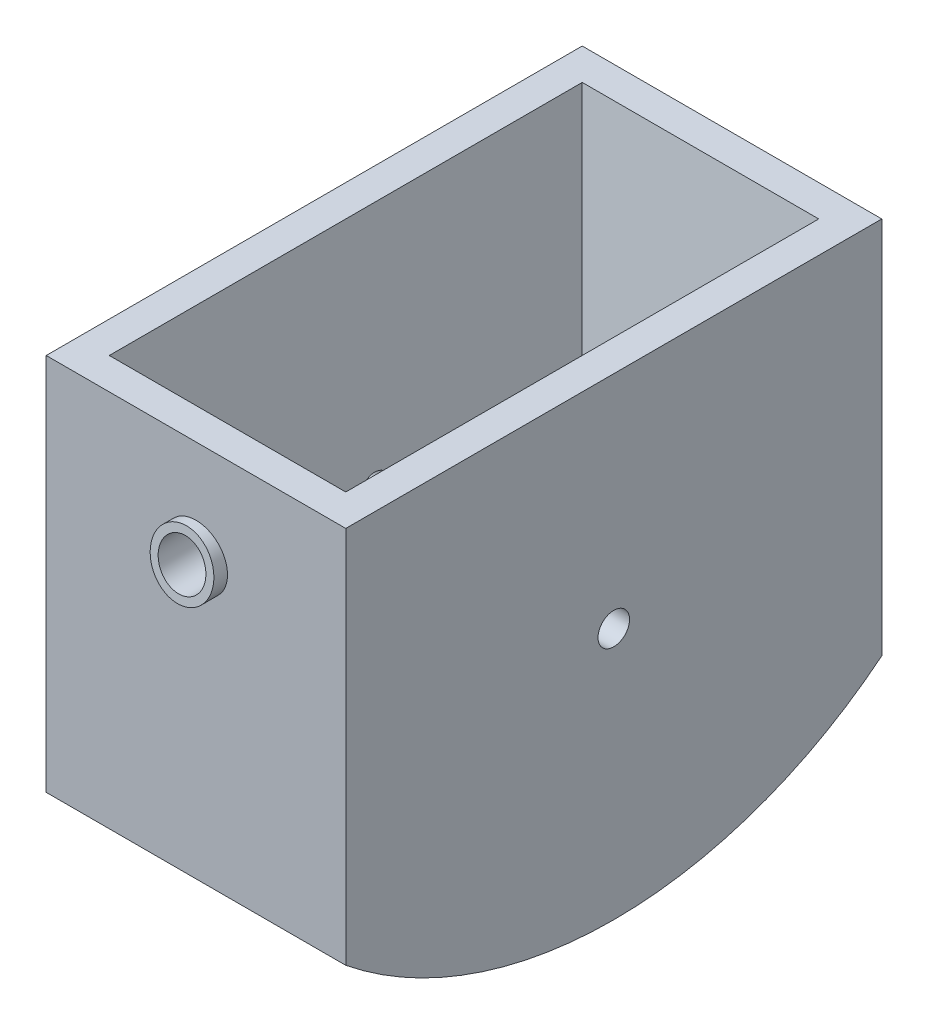
SolidWorks part; units mm, degrees
note: The reader was unsure of these and kept them because the rebuilt part matched: shared geometry of "Sketch2<3>".
ref_plane "Front Plane" through (0, 0, 0) normal (0, 0, 1) x (1, 0, 0)
ref_plane "Top Plane" through (0, 0, 0) normal (0, 1, 0) x (1, 0, 0)
ref_plane "Right Plane" through (0, 0, 0) normal (1, 0, 0) x (0, 0, -1)
sketch "Sketch1" plane through (0, 0, 0) normal (0, 1, 0) x (1, 0, 0)
  line L1 (-95, -170) -> (95, -170)
  line L2 (-95, -170) -> (-95, 170)
  line L3 (-95, 170) -> (95, 170)
  line L4 (95, -170) -> (95, 170)
  line L5 (-95, -170) -> (95, 170) construction
  line L6 (-95, 170) -> (95, -170) construction
  point P0 (0, 0)
  dimension "D1" = 340
  dimension "D2" = 190
extrude "Boss-Extrude1" add sketch "Sketch1" along normal blind 300
sketch "Sketch2" plane through (0, 0, 170) normal (0, 0, 1) x (1, 0, 0)
  line L0 (-95, 300) -> (95, 300)
  line L1 (-95, 237) -> (95, 237)
  circle A0 centre (0, 237) radius 15
  circle A2 centre (0, 237) radius 20
  dimension "D2" = 5
  dimension "D3" = 190
  dimension "D1" = 63
extrude "Boss-Extrude2" add sketch "Sketch2" along normal blind 57 contours L1 A2 A0 | L1 A0 | L1 A0 | L1 A2 A0
sketch "Sketch5" plane through (-95, 0, 0) normal (-1, 0, 0) x (0, 0, 1)
  line L0 (0, 300) -> (0, 160)
  line L1 (-170, 300) -> (170, 300) construction
  circle A0 centre (0, 160) radius 10
  dimension "D1" = 140
extrude "Cut-Extrude1" cut sketch "Sketch5" along normal through all from surface at -190 starting at face at (95, 150, 0)
sketch "Sketch9" plane through (-95, 0, 0) normal (-1, 0, 0) x (0, 0, 1)
  line L0 (-170, 300) -> (-170, 0) construction
  line L1 (-170, 0) -> (170, 0) construction
  line L2 (0, 300) -> (0, 0)
  line L3 (-170, 300) -> (170, 300) construction
  arc A0 (-170, 60) -> (0, 0) centre (-0.0012, 270.83) ccw
  arc A1 (170, 60) -> (0, 0) centre (0.0012, 270.83) cw
  point P0 (0, 0)
  point P1 (-170, 60)
  line M3 (-170, 0) -> (170, 0)
  line M4 (170, 0) -> (170, 300)
  line M6 (-170, 300) -> (-170, 0)
  dimension "D1" = 60
extrude "Cut-Extrude2" cut sketch "Sketch9" against normal through all contours A0 M6 M3 | A1 M4 M3
sketch "Sketch10" plane through (0, 300, 0) normal (0, 1, 0) x (1, 0, 0)
  line L0 (-75, 150) -> (-75, -150)
  line L1 (-95, 170) -> (95, 170)
  line L2 (-95, 170) -> (-95, -170)
  line L3 (-95, -170) -> (95, -170)
  line L4 (95, 170) -> (95, -170)
  line L5 (-75, -150) -> (75, -150)
  line L6 (75, 150) -> (75, -150)
  line L7 (-75, 150) -> (75, 150)
  dimension "D1" = 20
extrude "Cut-Extrude6" cut sketch "Sketch2<3>" against normal blind 236 contours L1 A0 | L1 A0
sketch "Sketch2<3>" plane through (0, 0, 170) normal (0, 0, 1) x (1, 0, 0) same geometry as "Sketch2"
extrude "Cut-Extrude7" cut sketch "Sketch10" against normal blind 301 draft 8 flip side to cut
